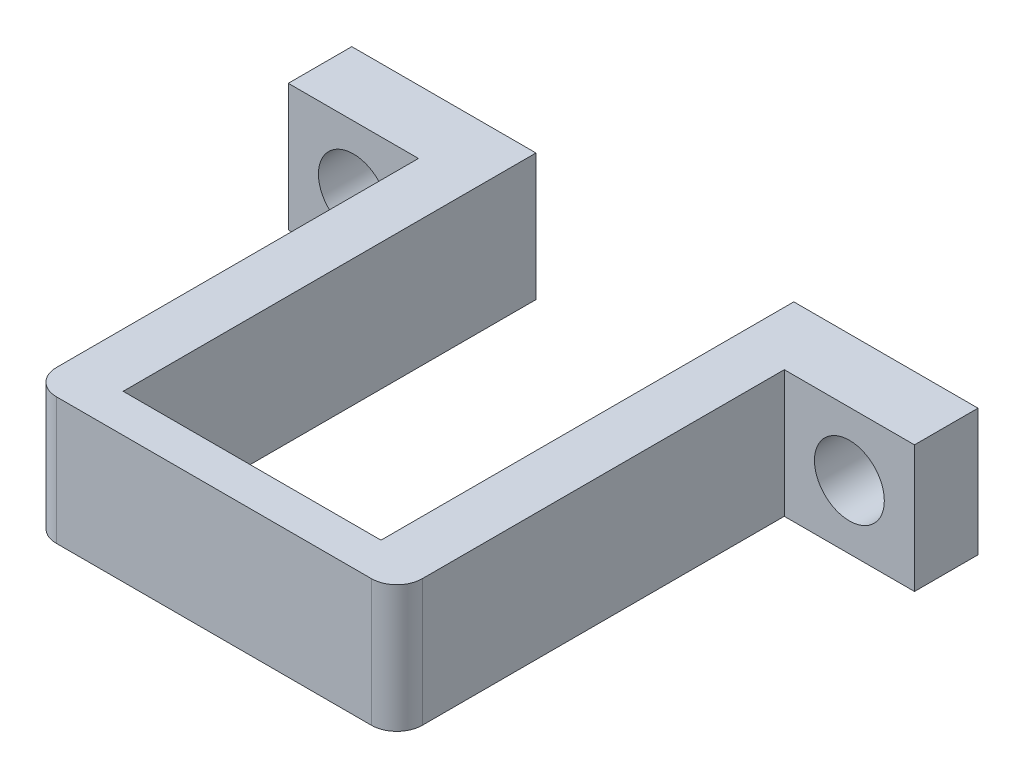
SolidWorks part; units mm, degrees
ref_plane "Front Plane" through (0, 0, 0) normal (0, 0, 1) x (1, 0, 0)
ref_plane "Top Plane" through (0, 0, 0) normal (0, 1, 0) x (1, 0, 0)
ref_plane "Right Plane" through (0, 0, 0) normal (1, 0, 0) x (0, 0, -1)
sketch "Sketch2" plane through (0, 0, 0) normal (0, 0, 1) x (1, 0, 0)
  line L0 (-10.15, -59.5) -> (-14.4, -59.5)
  line L2 (-14.4, -54.5) -> (-14.4, -3) construction
  line L3 (10.15, -59.5) -> (14.4, -59.5)
  line L5 (14.4, -54.5) -> (14.4, -3) construction
  line L6 (-11.4, -78) -> (-11.4, -38.8) construction
  line L7 (11.4, -78) -> (11.4, -38.8) construction
  line L8 (-11.4, -78) -> (-11.4, -38.8)
  line L9 (11.4, -78) -> (11.4, -38.8)
  line L10 (-10.15, -54.5) -> (-14.4, -54.5)
  line L11 (10.15, -64.5) -> (14.4, -64.5)
  line L12 (-10.15, -64.5) -> (-14.4, -64.5)
  line L13 (10.15, -54.5) -> (14.4, -54.5)
  line L14 (10, -54.5) -> (14.4, -54.5) construction
  line L15 (-10, -54.5) -> (-14.4, -54.5) construction
  line L16 (-10, -59.5) -> (-14.4, -59.5) construction
  line L17 (-10.15, -64.5) -> (-10.15, -54.5)
  line L18 (10.15, -64.5) -> (10.15, -54.5)
  line L19 (10, -64.5) -> (14.4, -64.5) construction
  line L20 (10, -59.5) -> (14.4, -59.5) construction
  line L21 (-10, -64.5) -> (-14.4, -64.5) construction
  line L22 (14.4, -64.5) -> (14.4, -54.5)
  line L23 (-14.4, -64.5) -> (-14.4, -54.5)
  line M5 (11.4, -3) -> (11.4, -35.8)
  line M7 (-11.4, -78) -> (-11.4, -38.8)
  line M12 (-14.4, -3) -> (-14.4, -54.5)
  line M14 (14.4, -54.5) -> (14.4, -3)
  dimension "D1" = 5
  dimension "D2" = 5
extrude "Boss-Extrude1" add sketch "Sketch2" along normal up to surface (32.5 mm away) contours L11 L3 M5 M14 | L13 L9 L3 M14 | L18 L3 L9 L13 | L18 L11 L3 M5 | L12 L8 L0 M12 | L12 L17 L0 L8 | L0 L17 L10 M7 | L10 L0 M7 M12 region at (-10.775, -62, 0) region at (-10.775, -57, 0) region at (-12.9, -62, 0) region at (-12.9, -57, 0) region at (10.775, -57, 0) region at (10.775, -62, 0) region at (12.9, -57, 0) region at (12.9, -62, 0)
sketch "Sketch3" plane through (0, 0, 32.5) normal (0, 0, 1) x (1, 0, 0)
  line L0 (10.15, -64.5) -> (-10.15, -64.5)
  line L1 (-10.15, -54.5) -> (10.15, -54.5)
  line L4 (-14.4, -64.5) -> (-10.15, -64.5)
  line L5 (-10.15, -64.5) -> (-10.15, -54.5)
  line L6 (-10.15, -54.5) -> (-14.4, -54.5)
  line L7 (-14.4, -54.5) -> (-14.4, -64.5)
  line L8 (-14.4, -64.5) -> (-10.15, -64.5)
  line L9 (-10.15, -64.5) -> (-10.15, -54.5)
  line L10 (-10.15, -54.5) -> (-14.4, -54.5)
  line L12 (14.4, -54.5) -> (10.15, -54.5)
  line L13 (10.15, -54.5) -> (10.15, -64.5)
  line L14 (10.15, -64.5) -> (14.4, -64.5)
  line L15 (14.4, -64.5) -> (14.4, -54.5)
  line L16 (14.4, -54.5) -> (10.15, -54.5)
  line L17 (10.15, -54.5) -> (10.15, -64.5)
  line L18 (10.15, -64.5) -> (14.4, -64.5)
  line L22 (-14.4, -54.5) -> (-14.4, -64.5)
  line L23 (14.4, -64.5) -> (14.4, -54.5)
  line M9 (-14.4, -64.5) -> (-10.15, -64.5)
  line M10 (-10.15, -64.5) -> (-10.15, -54.5)
  line M11 (-10.15, -54.5) -> (-14.4, -54.5)
  dimension "D1" = 0
  dimension "D2" = 0
extrude "Boss-Extrude2" add sketch "Sketch3" along normal blind 3 contours L18 L16 L17 | L17 L1 L0 M10 | M9 M10 M11 region at (0, -59.5, 32.5) region at (12.275, -59.5, 32.5) region at (-12.275, -59.5, 32.5)
sketch "Sketch4" plane through (0, 0, 0) normal (0, 0, -1) x (-1, 0, 0)
  line L0 (-10.15, -64.5) -> (-10.15, -54.5)
  line L1 (10.15, -54.5) -> (22.65, -54.5)
  line L2 (10.15, -54.5) -> (10.15, -64.5)
  line L4 (22.65, -54.5) -> (22.65, -64.5)
  line L5 (10.15, -64.5) -> (22.65, -64.5)
  line L6 (-10.15, -54.5) -> (-22.65, -54.5)
  line L7 (-10.15, -54.5) -> (-10.15, -64.5)
  line L8 (-10.15, -64.5) -> (-22.65, -64.5)
  line L9 (-22.65, -54.5) -> (-22.65, -64.5)
  line M6 (10.15, -64.5) -> (14.4, -64.5)
  line M7 (14.4, -64.5) -> (14.4, -54.5)
  line M8 (14.4, -54.5) -> (10.15, -54.5)
  line M9 (10.15, -54.5) -> (10.15, -64.5)
  dimension "D1" = 12.5
  dimension "D2" = 12.5
extrude "Boss-Extrude3" add sketch "Sketch4" against normal blind 3 contours L5 L4 L1 M7 | L6 L9 L8 L0 | M9 M6 M7 M8 region at (16.4, -59.5, 0) region at (-12.275, -59.5, 0) region at (-18.525, -59.5, 0)
sketch "Sketch5" plane through (0, 0, 0) normal (0, 0, -1) x (-1, 0, 0)
  line L0 (-22.65, -54.5) -> (-22.65, -64.5) construction
  line L1 (-22.65, -54.5) -> (-22.65, -64.5)
  line L2 (22.65, -54.5) -> (22.65, -64.5) construction
  line L3 (-22.65, -54.5) -> (-24.65, -54.5)
  line L4 (-22.65, -54.5) -> (-22.65, -64.5)
  line L5 (-22.65, -64.5) -> (-24.65, -64.5)
  line L6 (-24.65, -54.5) -> (-24.65, -64.5)
  line L7 (22.65, -54.5) -> (22.65, -64.5)
  line L9 (22.65, -54.5) -> (24.65, -54.5)
  line L10 (22.65, -54.5) -> (22.65, -64.5)
  line L11 (22.65, -64.5) -> (24.65, -64.5)
  line L12 (24.65, -54.5) -> (24.65, -64.5)
  line M4 (-22.65, -54.5) -> (-22.65, -64.5)
  dimension "D1" = 2
  dimension "D2" = 2
extrude "Boss-Extrude4" add sketch "Sketch5" against normal blind 3 contours L12 L9 L7 L11 | L3 L6 L5 M4 region at (23.65, -59.5, 0) region at (-23.65, -59.5, 0)
sketch "Sketch6" plane through (0, 0, 0) normal (0, 0, -1) x (-1, 0, 0)
  line L0 (-14.4, -64.5) -> (-14.4, -54.5)
  line L1 (-14.4, -80.5) -> (-14.4, -3) construction
  line L2 (-10.15, -54.5) -> (-24.65, -54.5) construction
  line L3 (-14.4, -54.5) -> (-24.65, -64.5)
  line L4 (14.4, -64.5) -> (14.4, -54.5)
  line L5 (14.4, -54.5) -> (24.65, -64.5)
  circle A0 centre (-19.525, -59.5) radius 2.75
  circle A1 centre (19.525, -59.5) radius 2.75
  dimension "D1" = 5.5
  dimension "D2" = 5.5
extrude "Cut-Extrude1" cut sketch "Sketch6" against normal blind 3 contours L5 A1 | L5 A1 | L3 A0 | L3 A0 region at (18.71, -60.3354, 0) region at (20.34, -58.6646, 0) region at (-20.34, -58.6646, 0) region at (-18.71, -60.3354, 0)
sketch "Sketch7" plane through (0, 0, 3) normal (0, 0, 1) x (1, 0, 0)
  line L0 (-24.65, -64.5) -> (-14.4, -64.5) construction
  line L1 (-14.4, -64.5) -> (-14.4, -54.5) construction
  line L2 (-14.4, -54.5) -> (-24.65, -54.5) construction
  line L3 (-24.65, -54.5) -> (-24.65, -64.5) construction
  line L4 (24.65, -54.5) -> (14.4, -54.5) construction
  line L5 (14.4, -54.5) -> (14.4, -64.5) construction
  line L6 (14.4, -64.5) -> (24.65, -64.5) construction
  line L7 (24.65, -64.5) -> (24.65, -54.5) construction
  line L8 (-24.65, -64.5) -> (-14.4, -64.5)
  line L9 (-14.4, -64.5) -> (-14.4, -54.5)
  line L10 (-14.4, -54.5) -> (-24.65, -54.5)
  line L11 (-24.65, -54.5) -> (-24.65, -64.5)
  line L12 (24.65, -54.5) -> (14.4, -54.5)
  line L13 (14.4, -54.5) -> (14.4, -64.5)
  line L14 (14.4, -64.5) -> (24.65, -64.5)
  line L15 (24.65, -64.5) -> (24.65, -54.5)
  circle A0 centre (-19.525, -59.5) radius 2.75 construction
  circle A1 centre (19.525, -59.5) radius 2.75 construction
  circle A2 centre (-19.525, -59.5) radius 2.75
  circle A3 centre (19.525, -59.5) radius 2.75
extrude "Boss-Extrude5" add sketch "Sketch7" along normal blind 2
fillet "Fillet1" radius 2 2 edges at (14.4, -59.5, 35.5) (-14.4, -59.5, 35.5)
